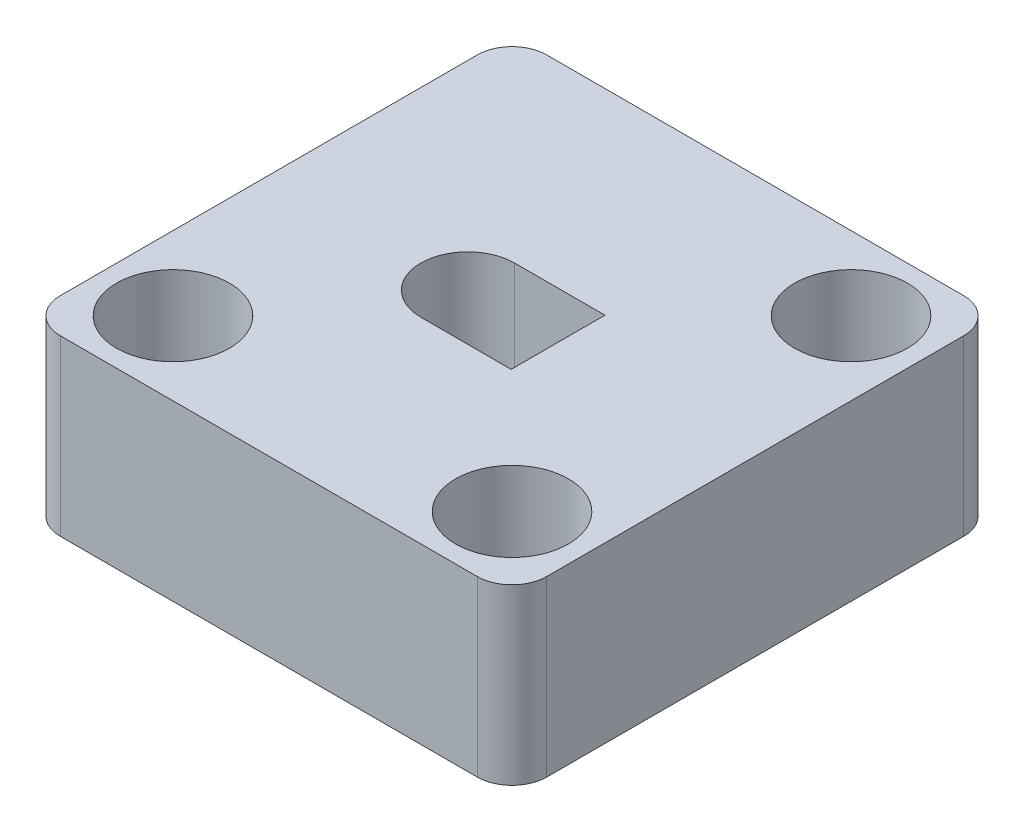
SolidWorks part; units mm, degrees
ref_plane "Front Plane" through (0, 0, 0) normal (0, 0, 1) x (1, 0, 0)
ref_plane "Top Plane" through (0, 0, 0) normal (0, 1, 0) x (1, 0, 0)
ref_plane "Right Plane" through (0, 0, 0) normal (1, 0, 0) x (0, 0, -1)
sketch "Sketch1" plane through (0, 0, 0) normal (0, 1, 0) x (1, 0, 0)
  line L0 (0.9332, 0.6825) -> (28.9332, 0.6825)
  line L1 (0.9332, 0.6825) -> (0.9332, 28.6825)
  line L2 (0.9332, 28.6825) -> (28.9332, 28.6825)
  line L3 (28.9332, 0.6825) -> (28.9332, 28.6825)
  line L4 (17.3832, 17.1825) -> (17.3832, 12.1825) construction
  line L5 (17.3832, 12.1825) -> (12.3832, 12.1825) construction
  line L6 (17.3832, 17.1825) -> (12.3832, 17.1825) construction
  line L7 (0.9332, 0.6825) -> (5.1758, 4.9251) construction
  line L8 (5.1758, 4.9251) -> (24.6905, 24.4399) construction
  line L9 (24.6905, 24.4399) -> (28.9332, 28.6825) construction
  line L10 (24.6905, 24.4399) -> (24.6905, 4.9251) construction
  line L11 (24.6905, 4.9251) -> (5.1758, 4.9251) construction
  line L12 (17.5832, 17.3825) -> (17.5832, 11.9825)
  line L13 (17.5832, 11.9825) -> (12.3832, 11.9825)
  line L14 (17.5832, 17.3825) -> (12.3832, 17.3825)
  line L15 (12.3832, 14.6825) -> (12.3832, 12.1325) construction
  circle A0 centre (5.1758, 4.9251) radius 3.25
  circle A1 centre (24.6905, 4.9251) radius 3.25
  circle A2 centre (24.6905, 24.4399) radius 3.25
  arc A3 (12.3832, 17.1825) -> (12.3832, 12.1825) centre (12.3832, 14.6825) ccw construction
  arc A4 (12.3832, 17.3825) -> (12.3832, 11.9825) centre (12.3832, 14.6825) ccw
  dimension "D2" = 6.5
  dimension "D6" = 5
  dimension "D1" = 28
  dimension "D3" = 6
  dimension "D4" = 2.55
  dimension "D5" = 5
  dimension "D7" = 11.45
  dimension "D8" = 0.2
extrude "Boss-Extrude1" add sketch "Sketch1" along normal blind 10
fillet "Fillet1" radius 2 4 edges at (0.9332, 5, -0.6825) (0.9332, 5, -28.6825) (28.9332, 5, -28.6825) (28.9332, 5, -0.6825)
